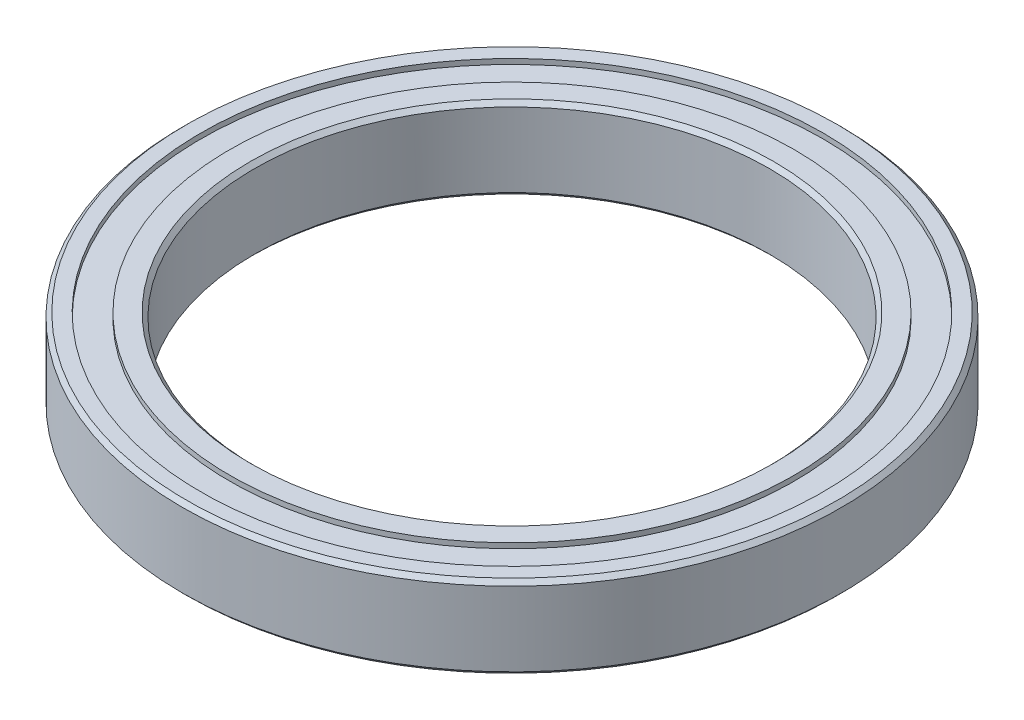
SolidWorks part; units mm, degrees
ref_plane "Ebene vorne" through (0, 0, 0) normal (0, 0, 1) x (1, 0, 0)
ref_plane "Ebene oben" through (0, 0, 0) normal (0, 1, 0) x (1, 0, 0)
ref_plane "Ebene rechts" through (0, 0, 0) normal (1, 0, 0) x (0, 0, -1)
sketch "Skizze2" plane through (0, 0, 0) normal (1, 0, 0) x (0, 0, -1)
  line L0 (0, -18.1229) -> (0, 17.8232) construction
  line L1 (-24.3396, 0) -> (24.2431, 0) construction
  line L2 (-16, 2) -> (-16, -2)
  line L3 (-16, -2) -> (-15.1, -2)
  line L4 (-15.1, -2) -> (-15.1, -1.75)
  line L5 (-15.1, -1.75) -> (-13.7, -1.75)
  line L6 (-13.7, -1.75) -> (-13.7, -2)
  line L7 (-13.7, -2) -> (-12.5, -2)
  line L8 (-12.5, -2) -> (-12.5, 2)
  line L9 (-13.7, 2) -> (-12.5, 2)
  line L10 (-13.7, 1.75) -> (-13.7, 2)
  line L11 (-15.1, 1.75) -> (-13.7, 1.75)
  line L12 (-15.1, 2) -> (-15.1, 1.75)
  line L13 (-16, 2) -> (-15.1, 2)
  point P5 (-12.5, 0)
  point P19 (-16, 0)
  dimension "D1" = 32
  dimension "D2" = 25
  dimension "D3" = 4
  dimension "D4" = 30.2
  dimension "D5" = 27.4
  dimension "D6" = 0.25
revolve "Rotation2" add sketch "Skizze2" angle 360 about L0
ref_axis "Achse1" through (0, -2.2, 0) along (0, 1, 0)
chamfer "Fase1" distance 0.2 angle 45 4 edges at (0, 2, -12.5) (0, -2, -12.5) (0, 2, -16) (0, -2, -16)
